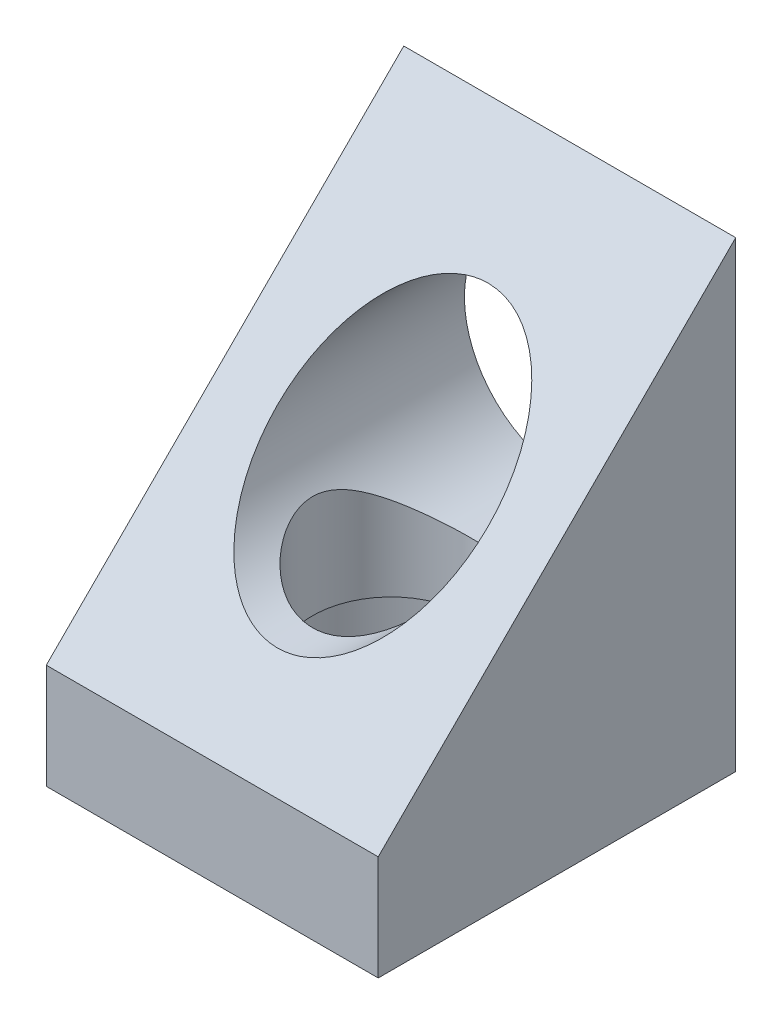
SolidWorks part; units mm, degrees
ref_plane "Front Plane" through (0, 0, 0) normal (0, 0, 1) x (1, 0, 0)
ref_plane "Top Plane" through (0, 0, 0) normal (0, 1, 0) x (1, 0, 0)
ref_plane "Right Plane" through (0, 0, 0) normal (1, 0, 0) x (0, 0, -1)
sketch "Sketch1" plane through (0, 0, 0) normal (1, 0, 0) x (0, 0, -1)
  line L0 (0, 0) -> (28, 0)
  line L1 (28, 0) -> (28, 36.22)
  line L2 (28, 36.22) -> (0, 8.22)
  line L3 (0, 8.22) -> (0, 0)
  dimension "D1" = 28
  dimension "D2" = 8.22
  dimension "D3" = 135
extrude "Boss-Extrude1" add sketch "Sketch1" along normal blind 26
sketch "Sketch2" plane through (0, 0, -28) normal (0, 0, -1) x (-1, 0, 0)
  line L0 (-26, 0) -> (0, 0) construction
  line L1 (-26, 36.22) -> (0, 36.22) construction
  circle A0 centre (-13, 21.58) radius 8.25
  point P4 (0, 0)
  point P7 (-13, 36.22)
  dimension "D1" = 16.5
  dimension "D2" = 21.58
extrude "Cut-Extrude1" cut sketch "Sketch2" against normal through all
sketch "Sketch3" plane through (0, 0, 0) normal (0, -1, 0) x (1, 0, 0)
  line L0 (26, -28) -> (0, -28) construction
  line L1 (26, 0) -> (26, -28) construction
  circle A0 centre (13, -14) radius 6.15
  point P2 (0, 0)
  point P5 (13, -28)
  point P8 (26, -14)
  dimension "D1" = 12.3
extrude "Cut-Extrude2" cut sketch "Sketch3" against normal through all
sketch "Sketch4" plane through (0, 0, 0) normal (0, -1, 0) x (1, 0, 0)
  line L0 (0, 0) -> (0, -28) construction
  line L1 (26, 0) -> (0, 0) construction
  line L2 (26, 0) -> (26, -28) construction
  line L3 (26, -28) -> (0, -28) construction
  circle A0 centre (13, -14) radius 10.325
  circle A1 centre (3.9, -3.85) radius 1.25
  circle A2 centre (23.05, -3.75) radius 1.25
  circle A3 centre (22.85, -22.95) radius 1.25
  circle A4 centre (3.7, -22.65) radius 1.25
  dimension "D1" = 20.65
  dimension "D2" = 2.5
  dimension "D5" = 2.5
  dimension "D8" = 2.5
  dimension "D11" = 2.5
  dimension "D3" = 3.9
  dimension "D4" = 3.85
  dimension "D6" = 2.95
  dimension "D7" = 3.75
  dimension "D9" = 5.05
  dimension "D10" = 3.15
  dimension "D12" = 5.35
  dimension "D13" = 3.7
extrude "Cut-Extrude3" cut sketch "Sketch4" against normal blind 8
